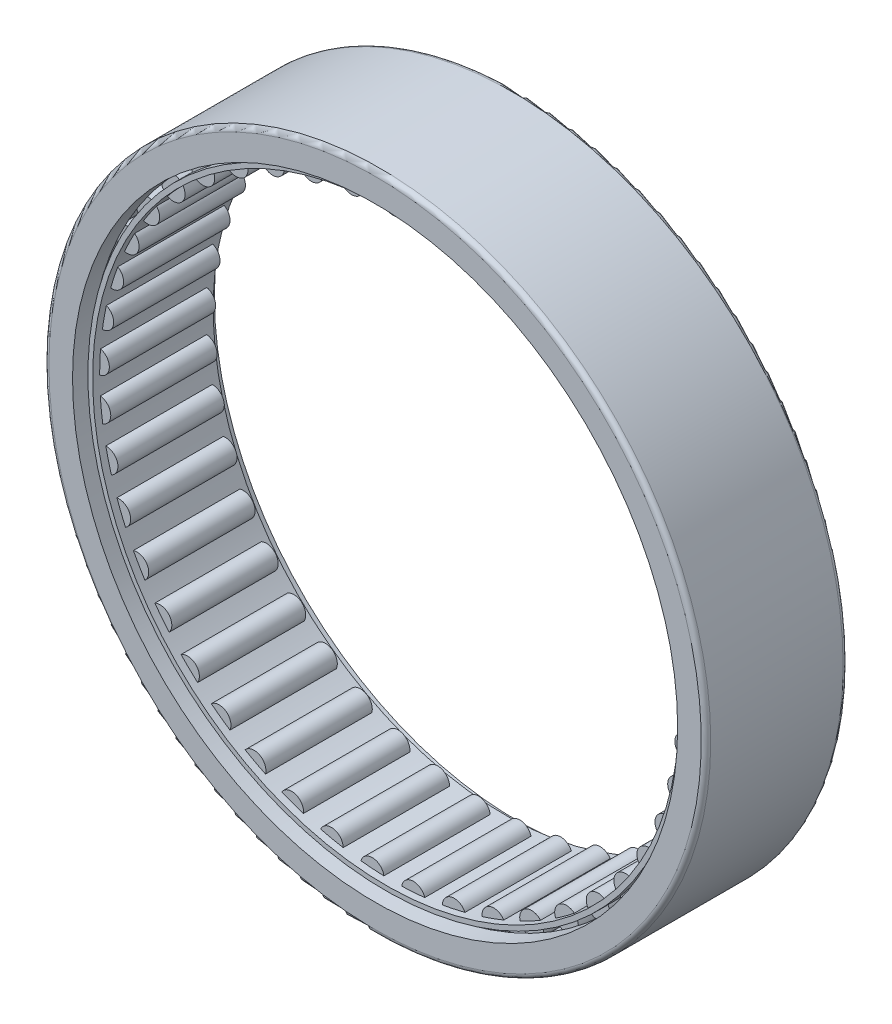
SolidWorks part; units mm, degrees
ref_plane "Front Plane" through (0, 0, 0) normal (0, 0, 1) x (1, 0, 0)
ref_plane "Top Plane" through (0, 0, 0) normal (0, 1, 0) x (1, 0, 0)
ref_plane "Right Plane" through (0, 0, 0) normal (1, 0, 0) x (0, 0, -1)
sketch "BaseSke" plane through (0, 0, 0) normal (1, 0, 0) x (0, 0, -1)
  line L0 (-47.2296, 0) -> (24.6132, 0) construction
  line L1 (-47.2296, 62.5) -> (24.6132, 62.5) construction
  line L2 (0, 129.5214) -> (0, -86.3012) construction
  line L3 (-11.25, 62.5) -> (-11.25, 65) construction
  line L4 (-15, 70) -> (15, 70) construction
  line L5 (-15, 55) -> (15, 55) construction
  line L6 (-11.25, 60) -> (11.25, 60)
  line L7 (-11.25, 60) -> (-11.25, 62.5)
  line L8 (-11.25, 62.5) -> (11.25, 62.5)
  line L9 (11.25, 60) -> (11.25, 62.5)
  line L10 (-11.25, 65) -> (11.25, 65) construction
  line L11 (11.25, 65) -> (11.25, 62.5) construction
  dimension "D2" = 22.5
  dimension "D1" = 125
revolve "Roller" add sketch "BaseSke" angle 360 about L8
sketch "OuterRaceSke" plane through (0, 0, 0) normal (1, 0, 0) x (0, 0, -1)
  line L0 (0, 0) -> (0, 87.5396) construction
  line L1 (-15, 70) -> (15, 70)
  line L2 (-15, 70) -> (-15, 64)
  line L3 (-15, 64) -> (-11.275, 64)
  line L4 (15, 70) -> (15, 64)
  line L5 (-50.3916, 0) -> (55.2197, 0) construction
  line L6 (-11.25, 65) -> (11.25, 65) construction
  line L7 (11.275, 64) -> (15, 64)
  line L9 (-11.275, 64) -> (-11.275, 64.98)
  line L10 (-11.275, 64.98) -> (11.275, 64.98)
  line L11 (11.275, 64) -> (11.275, 64.98)
  dimension "D2" = 128
  dimension "D1" = 22.55
  dimension "D3" = 0.02
revolve "OuterRace" add sketch "OuterRaceSke" angle 360 about L5
sketch "CageSke" plane through (0, 0, 0) normal (1, 0, 0) x (0, 0, -1)
  line L0 (-70.8626, 0) -> (113.5527, 0) construction
  line L1 (0, 58.441) -> (0, -70.8113) construction
  line L2 (-12.75, 62) -> (12.75, 62)
  line L3 (-12.75, 62) -> (-12.75, 63)
  line L4 (-33.2996, 62.5) -> (13.017, 62.5) construction
  line L5 (-47.2296, 62.5) -> (24.6132, 62.5) construction
  line L6 (0, 129.5214) -> (0, -86.3012) construction
  line L7 (-12.75, 63) -> (12.75, 63)
  line L9 (12.75, 62) -> (12.75, 63)
  point P17 (0, 62)
  dimension "D1" = 25.5
  dimension "D2" = 1
revolve "Cage" add sketch "CageSke" angle 360 about L0
fillet "Fillet1" radius 1 2 edges at (70, 0, -15) (70, 0, 15)
pattern_circular "CirPatternBall" count 45 over 360 about axis through (0, 0, 50.3916) along (0, 0, -1) of "Roller"
sketch "SimplifiedSke" plane through (0, 0, 0) normal (1, 0, 0) x (0, 0, -1)
  line L0 (37.5911, 0) -> (-37.5911, 0) construction
  line L1 (-13.1351, 62.5) -> (13.151, 62.5) construction
  line L2 (-11.25, 65) -> (11.25, 65)
  line L3 (-11.25, 65) -> (-11.25, 60)
  line L4 (-11.25, 60) -> (11.25, 60)
  line L5 (11.25, 65) -> (11.25, 60)
  line L6 (-47.2296, 62.5) -> (24.6132, 62.5) construction
revolve "Simplified" [suppressed] add sketch "SimplifiedSke" angle 360 about L0
equation "\"D2@BaseSke\" = \"Bearing_Thickness@BaseSke\"*0.75"
equation "\"D1@BaseSke\" =  ( \"Bearing_Outside_Diameter@BaseSke\" + \"Bearing_Inside_Diameter@BaseSke\" )  / 2"
equation "\"D1@OuterRaceSke\" = \"Bearing_Thickness@BaseSke\"*0.75+0.05"
equation "\"D2@OuterRaceSke\" =\"Bearing_Outside_Diameter@BaseSke\" -  ( \"Bearing_Outside_Diameter@BaseSke\" - \"Bearing_Inside_Diameter@BaseSke\"  )/ 2.5 "
equation "\"D1@CageSke\" = \"Bearing_Thickness@BaseSke\"*0.75+3"
equation "\"D2@CageSke\" = ( \"Bearing_Outside_Diameter@BaseSke\" - \"Diameter_Fw@BaseSke\" ) *0.05"
equation "\"D1@CirPatternBall\" =  int(  ( \"Bearing_Outside_Diameter@BaseSke\" + \"Bearing_Inside_Diameter@BaseSke\" )  / 2 *  pi  /  ( \"Bearing_Outside_Diameter@BaseSke\" - \"Bearing_Inside_Diameter@BaseSke\" ) * 3.5 ) "
